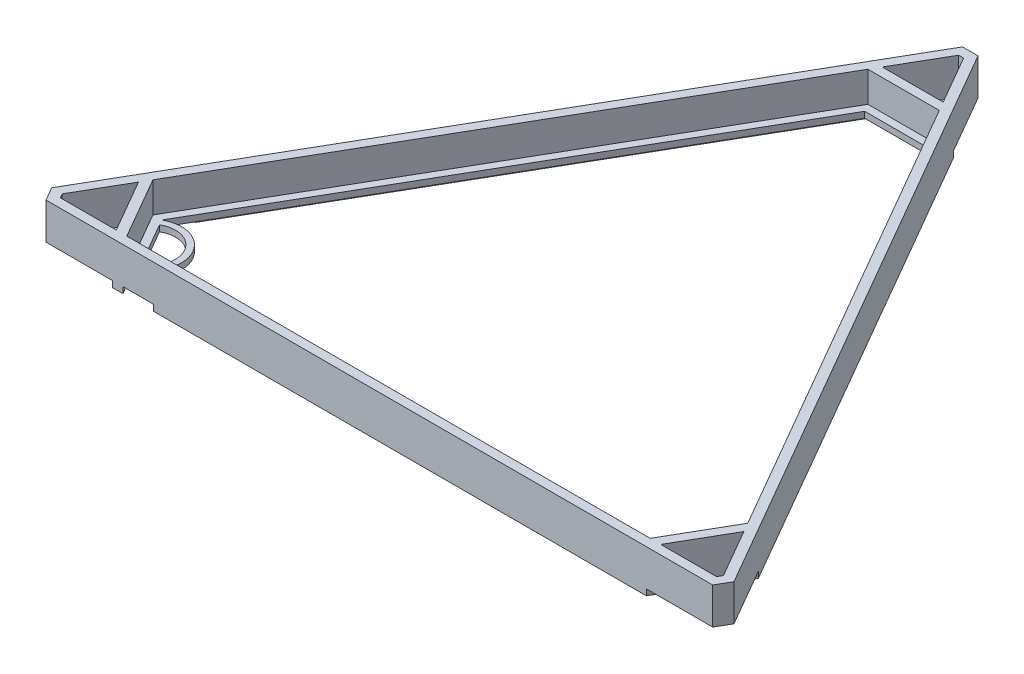
SolidWorks part; units mm, degrees
ref_plane "Front Plane" through (0, 0, 0) normal (0, 0, 1) x (1, 0, 0)
ref_plane "Top Plane" through (0, 0, 0) normal (0, 1, 0) x (1, 0, 0)
ref_plane "Right Plane" through (0, 0, 0) normal (1, 0, 0) x (0, 0, -1)
sketch "Sketch1" plane through (0, 0, 0) normal (0, 1, 0) x (1, 0, 0)
  line L17 (-4, 192.2576) -> (111, -6.9282) construction
  line L24 (4, 192.2576) -> (-111, -6.9282) construction
  line L25 (-115, 0) -> (115, 0) construction
  line L26 (0, -4.4282) -> (0, -1.4282) construction
  line L27 (-113, -3.4641) -> (-107, 0) construction
  line L28 (0, 192.2576) -> (0, 185.3294) construction
  line L29 (113, -3.4641) -> (107, 0) construction
  line L31 (-107.8246, -1.4282) -> (-108.6491, 0)
  line L39 (109.5566, -4.4282) -> (-109.5566, -4.4282)
  line L40 (-0.8246, 186.7576) -> (0.8246, 186.7576)
  line L41 (-109.5566, -4.4282) -> (-112.1132, 0)
  line L42 (-2.5566, 189.7576) -> (-112.1132, 0)
  line L43 (109.5566, -4.4282) -> (112.1132, 0)
  line L44 (-2.5566, 189.7576) -> (2.5566, 189.7576)
  line L45 (2.5566, 189.7576) -> (112.1132, 0)
  line L47 (108.6491, 0) -> (107.8246, -1.4282)
  line L50 (-99.4737, 15.8923) -> (-89.4737, -1.4282)
  line L51 (-107.8246, -1.4282) -> (-89.4737, -1.4282)
  line L52 (-99.4737, 15.8923) -> (-108.6491, 0)
  line L54 (89.4737, -1.4282) -> (107.8246, -1.4282)
  line L56 (89.4737, -1.4282) -> (99.4737, 15.8923)
  line L57 (99.4737, 15.8923) -> (108.6491, 0)
  line L58 (0, -1.4282) -> (0, 1.0718) construction
  line L59 (54.7369, 93.3788) -> (52.5718, 92.1288) construction
  line L62 (-10, 170.8653) -> (10, 170.8653)
  line L63 (-10, 170.8653) -> (-0.8246, 186.7576)
  line L64 (0.8246, 186.7576) -> (10, 170.8653)
  line L65 (94.4737, 7.2321) -> (91.8756, 8.7321) construction
  line L66 (-11.7321, 167.8653) -> (11.7321, 167.8653)
  line L67 (97.7417, 18.8923) -> (86.0096, -1.4282)
  line L68 (97.7417, 18.8923) -> (11.7321, 167.8653)
  line L69 (-54.7369, 93.3788) -> (-52.5718, 92.1288) construction
  line L70 (-84.5662, 1.0718) -> (84.5662, 1.0718)
  line L71 (-94.4737, 7.2321) -> (-91.8756, 8.7321) construction
  line L72 (-97.7417, 18.8923) -> (-86.0096, -1.4282)
  line L73 (-86.0096, -1.4282) -> (86.0096, -1.4282)
  line L74 (-97.7417, 18.8923) -> (-11.7321, 167.8653)
  line L75 (94.8549, 18.8923) -> (10.2887, 165.3653)
  line L76 (-10.2887, 165.3653) -> (-94.8549, 18.8923)
  line L79 (91.8756, 8.7321) -> (89.7106, 9.9821) construction
  line L80 (94.8549, 18.8923) -> (84.5662, 1.0718)
  line L81 (0, 167.8653) -> (0, 165.3653) construction
  line L82 (-10.2887, 165.3653) -> (10.2887, 165.3653)
  line L97 (-94.8549, 18.8923) -> (-84.5662, 1.0718) construction
  line L100 (-94.8549, 18.8923) -> (-93.8549, 17.1603) construction
  line L106 (-84.5662, 1.0718) -> (-85.5662, 2.8038) construction
  line L107 (-93.8549, 17.1603) -> (-85.5662, 2.8038)
  arc A0 (-94.8549, 18.8923) -> (-84.5662, 1.0718) centre (-89.7106, 9.9821) cw
  arc A1 (-93.8549, 17.1603) -> (-85.5662, 2.8038) centre (-89.7106, 9.9821) cw
  point P18 (0, -1.4282)
  point P41 (0, 167.8653)
  point P44 (91.8756, 8.7321)
  point P51 (-91.8756, 8.7321)
  point P55 (0, 1.0718)
  point P57 (-52.5718, 92.1288)
  point P61 (52.5718, 92.1288)
  point P69 (89.7106, 9.9821)
  point P74 (0, 165.3653)
  point P78 (-89.7106, 9.9821)
  point P83 (-89.7106, 9.9821)
  dimension "D1" = 8
  dimension "D2" = 8
  dimension "D3" = 8
  dimension "D4" = 230
  dimension "D5" = 230
  dimension "D6" = 230
  dimension "D7" = 3
  dimension "D8" = 3
  dimension "D9" = 3
  dimension "D10" = 2.5
  dimension "D11" = 2.5
  dimension "D12" = 2.5
  dimension "D13" = 2
  dimension "D14" = 2.5
  dimension "D15" = 2.5
  dimension "D16" = 2
extrude "Boss-Extrude1" add sketch "Sketch1" along normal blind 12 contours L45 L43 L39 L41 L42 L44 | L74 L66 L68 L67 L73 L72 | L52 L31 L51 L50 | L57 L47 L54 L56 | L64 L62 L63 L40
extrude "Boss-Extrude2" add sketch "Sketch1<4>" along normal blind 2 contours L74 L72 L73 L67 L68 L66 L76 L82 L75 L80 L70 region at (0, 0, -167.6067)
sketch "Sketch1<4>" plane through (0, 0, 0) normal (0, 1, 0) x (1, 0, 0) same geometry as "Sketch1"
sketch "Sketch2" plane through (0, 0, 0) normal (0, -1, 0) x (1, 0, 0)
  line L24 (-2.5566, -189.7576) -> (-112.1132, 0) construction
  line L25 (109.5566, 4.4282) -> (-109.5566, 4.4282) construction
  line L27 (2.5566, -189.7576) -> (112.1132, 0) construction
  line L33 (-87.7417, 4.4282) -> (-101.2058, -18.8923)
  line L34 (87.7417, 4.4282) -> (-74.2776, 4.4282)
  line L35 (-11.7321, -167.8653) -> (11.7321, -167.8653)
  line L36 (89.4737, 1.4282) -> (87.7417, 4.4282) construction
  line L37 (99.4737, -15.8923) -> (101.2058, -18.8923) construction
  line L38 (86.0096, 1.4282) -> (97.7417, -18.8923)
  line L39 (-84.2776, 4.4282) -> (-74.2776, 4.4282) construction
  line L40 (101.2058, -18.8923) -> (87.7417, 4.4282)
  line L41 (-86.0096, 1.4282) -> (-76.0096, 1.4282) construction
  line L42 (-10, -170.8653) -> (-13.4641, -170.8653) construction
  line L43 (10, -170.8653) -> (13.4641, -170.8653) construction
  line L46 (57.3349, -94.8788) -> (54.7369, -93.3788) construction
  line L47 (0, 4.4282) -> (0, 1.4282) construction
  line L49 (11.7321, -167.8653) -> (97.7417, -18.8923)
  line L51 (-57.3349, -94.8788) -> (-54.7369, -93.3788) construction
  line L54 (-13.4641, -170.8653) -> (13.4641, -170.8653)
  line L55 (13.4641, -170.8653) -> (101.2058, -18.8923)
  line L56 (-84.2776, 4.4282) -> (-99.4737, -21.8923)
  line L57 (109.5566, 4.4282) -> (-109.5566, 4.4282) construction
  line L58 (-84.2776, 4.4282) -> (-87.7417, 4.4282)
  line L59 (-2.5566, -189.7576) -> (-112.1132, 0) construction
  line L60 (-99.4737, -21.8923) -> (-101.2058, -18.8923)
  line L61 (-86.0096, 1.4282) -> (86.0096, 1.4282) construction
  line L62 (-74.2776, 4.4282) -> (-76.0096, 1.4282)
  line L63 (-76.0096, 1.4282) -> (86.0096, 1.4282)
  line L64 (-97.7417, -18.8923) -> (-92.7417, -27.5526) construction
  line L65 (-97.7417, -18.8923) -> (-11.7321, -167.8653) construction
  line L66 (-99.4737, -21.8923) -> (-94.4737, -30.5526) construction
  line L67 (-94.4737, -30.5526) -> (-92.7417, -27.5526)
  line L68 (-92.7417, -27.5526) -> (-11.7321, -167.8653)
  line L69 (-13.4641, -170.8653) -> (-94.4737, -30.5526)
  point P66 (0, -167.8653)
  point P68 (-91.8756, -8.7321)
  point P72 (54.7369, -93.3788)
  point P75 (0, 1.4282)
  point P80 (-54.7369, -93.3788)
  dimension "D1" = 10
  dimension "D2" = 10
  dimension "D3" = 10
  dimension "D4" = 3
  dimension "D5" = 3
  dimension "D6" = 3
  dimension "D7" = 10
extrude "Boss-Extrude3" add sketch "Sketch2" along normal blind 2
